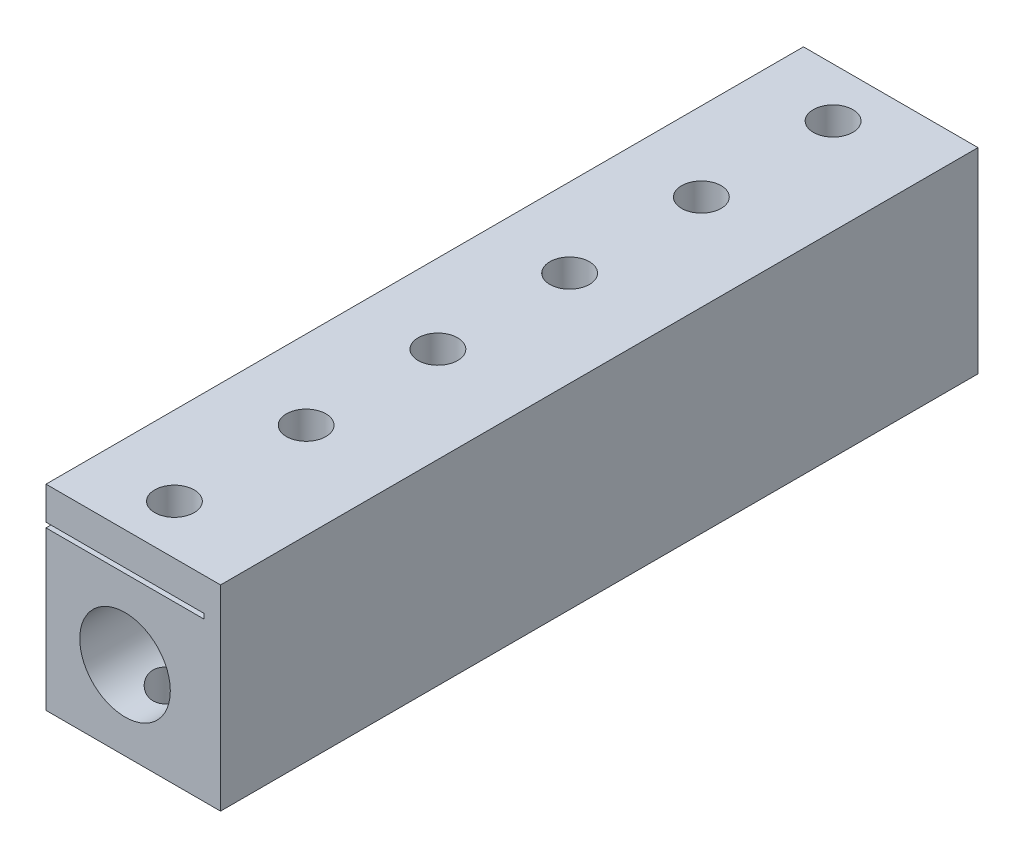
SolidWorks part; units mm, degrees
ref_plane "Front Plane" through (0, 0, 0) normal (0, 0, 1) x (1, 0, 0)
ref_plane "Top Plane" through (0, 0, 0) normal (0, 1, 0) x (1, 0, 0)
ref_plane "Right Plane" through (0, 0, 0) normal (1, 0, 0) x (0, 0, -1)
sketch "Sketch1" plane through (0, 0, 0) normal (0, 0, 1) x (1, 0, 0)
  line L1 (-24, -24) -> (24, -24)
  line L2 (-24, -24) -> (-24, 24)
  line L3 (-24, 24) -> (24, 24)
  line L4 (24, -24) -> (24, 24)
  line L5 (-24, -24) -> (24, 24) construction
  line L6 (-24, 24) -> (24, -24) construction
  line L7 (24, -24) -> (29, -24)
  line L8 (24, -24) -> (24, 35.5)
  line L9 (24, 35.5) -> (29, 35.5)
  line L10 (29, -24) -> (29, 35.5)
  line L11 (24, 35.5) -> (-24, 35.5)
  line L12 (24, 35.5) -> (24, 25.5)
  line L13 (24, 25.5) -> (-24, 25.5)
  line L14 (-24, 35.5) -> (-24, 25.5)
  circle A0 centre (0, 0) radius 13.75
  dimension "D1" = 27.5
  dimension "D2" = 1.5
  dimension "D3" = 48
  dimension "D4" = 48
  dimension "D5" = 5
  dimension "D6" = 10
extrude "Boss-Extrude1" add sketch "Sketch1" along normal blind 230 contours L1 L4 L3 L2 A0 | L11 L14 L13 L8 | L7 L10 L9 L8 L4 region at (-23.3212, 0, 0) region at (26.5, 5.75, 0) region at (0, 30.5, 0)
sketch "Sketch3" plane through (0, 35.5, 0) normal (0, 1, 0) x (1, 0, 0)
  line L0 (0, 0) -> (0, -230) construction
  line L1 (-24, -230) -> (29, -230) construction
  circle A0 centre (0, -15) radius 6
  circle A1 centre (0, -55) radius 6
  circle A2 centre (0, -95) radius 6
  circle A3 centre (0, -135) radius 6
  circle A4 centre (0, -175) radius 6
  circle A5 centre (0, -215) radius 6
  dimension "D1" = 12
  dimension "D2" = 15
  dimension "D4" = 15
  dimension "D3" = 6
extrude "Cut-Extrude1" cut sketch "Sketch3" against normal up to next
sketch "Sketch4" plane through (0, 35.5, 0) normal (0, 1, 0) x (1, 0, 0)
  line L0 (0, 0) -> (0, -230) construction
  line L1 (-24, -230) -> (29, -230) construction
  circle A0 centre (0, -15) radius 3.25
  circle A1 centre (0, -55) radius 3.25
  circle A2 centre (0, -95) radius 3.25
  circle A3 centre (0, -135) radius 3.25
  circle A4 centre (0, -175) radius 3.25
  circle A5 centre (0, -215) radius 3.25
  dimension "D1" = 6.5
  dimension "D2" = 6
extrude "Cut-Extrude2" cut sketch "Sketch4" against normal through all
sketch "Sketch5" plane through (0, -24, 0) normal (0, -1, 0) x (1, 0, 0)
  line L0 (0, 230) -> (0, 0) construction
  line L1 (-24, 230) -> (29, 230) construction
  circle A0 centre (0, 215) radius 6.5
  circle A1 centre (0, 175) radius 6.5
  circle A2 centre (0, 135) radius 6.5
  circle A3 centre (0, 95) radius 6.5
  circle A4 centre (0, 55) radius 6.5
  circle A5 centre (0, 15) radius 6.5
  dimension "D1" = 13
  dimension "D2" = 6
extrude "Cut-Extrude3" cut sketch "Sketch5" against normal up to next
sketch "Sketch7" plane through (0, 24, 0) normal (0, 1, 0) x (1, 0, 0)
  line L0 (0, 0) -> (0, -230) construction
  line L1 (0, -8.5337) -> (-5.6, -11.7668)
  line L2 (-5.6, -11.7668) -> (-5.6, -18.2332)
  line L3 (-5.6, -18.2332) -> (0, -21.4663)
  line L4 (0, -21.4663) -> (5.6, -18.2332)
  line L5 (5.6, -18.2332) -> (5.6, -11.7668)
  line L6 (5.6, -11.7668) -> (0, -8.5337)
  line L7 (-24, -230) -> (29, -230) construction
  line L8 (0, -48.5337) -> (-5.6, -51.7668)
  line L9 (-5.6, -51.7668) -> (-5.6, -58.2332)
  line L10 (-5.6, -58.2332) -> (0, -61.4663)
  line L11 (0, -61.4663) -> (5.6, -58.2332)
  line L12 (5.6, -58.2332) -> (5.6, -51.7668)
  line L13 (5.6, -51.7668) -> (0, -48.5337)
  line L14 (0, -88.5337) -> (-5.6, -91.7668)
  line L15 (-5.6, -91.7668) -> (-5.6, -98.2332)
  line L16 (-5.6, -98.2332) -> (0, -101.4663)
  line L17 (0, -101.4663) -> (5.6, -98.2332)
  line L18 (5.6, -98.2332) -> (5.6, -91.7668)
  line L19 (5.6, -91.7668) -> (0, -88.5337)
  line L20 (0, -128.5337) -> (-5.6, -131.7668)
  line L21 (-5.6, -131.7668) -> (-5.6, -138.2332)
  line L22 (-5.6, -138.2332) -> (0, -141.4663)
  line L23 (0, -141.4663) -> (5.6, -138.2332)
  line L24 (5.6, -138.2332) -> (5.6, -131.7668)
  line L25 (5.6, -131.7668) -> (0, -128.5337)
  line L26 (0, -168.5337) -> (-5.6, -171.7668)
  line L27 (-5.6, -171.7668) -> (-5.6, -178.2332)
  line L28 (-5.6, -178.2332) -> (0, -181.4663)
  line L29 (0, -181.4663) -> (5.6, -178.2332)
  line L30 (5.6, -178.2332) -> (5.6, -171.7668)
  line L31 (5.6, -171.7668) -> (0, -168.5337)
  line L32 (0, -208.5337) -> (-5.6, -211.7668)
  line L33 (-5.6, -211.7668) -> (-5.6, -218.2332)
  line L34 (-5.6, -218.2332) -> (0, -221.4663)
  line L35 (0, -221.4663) -> (5.6, -218.2332)
  line L36 (5.6, -218.2332) -> (5.6, -211.7668)
  line L37 (5.6, -211.7668) -> (0, -208.5337)
  circle A0 centre (0, -15) radius 5.6 construction
  dimension "D1" = 11.2
  dimension "D2" = 6
extrude "Cut-Extrude4" cut sketch "Sketch7" against normal up to next from offset 5 offset against normal yes
